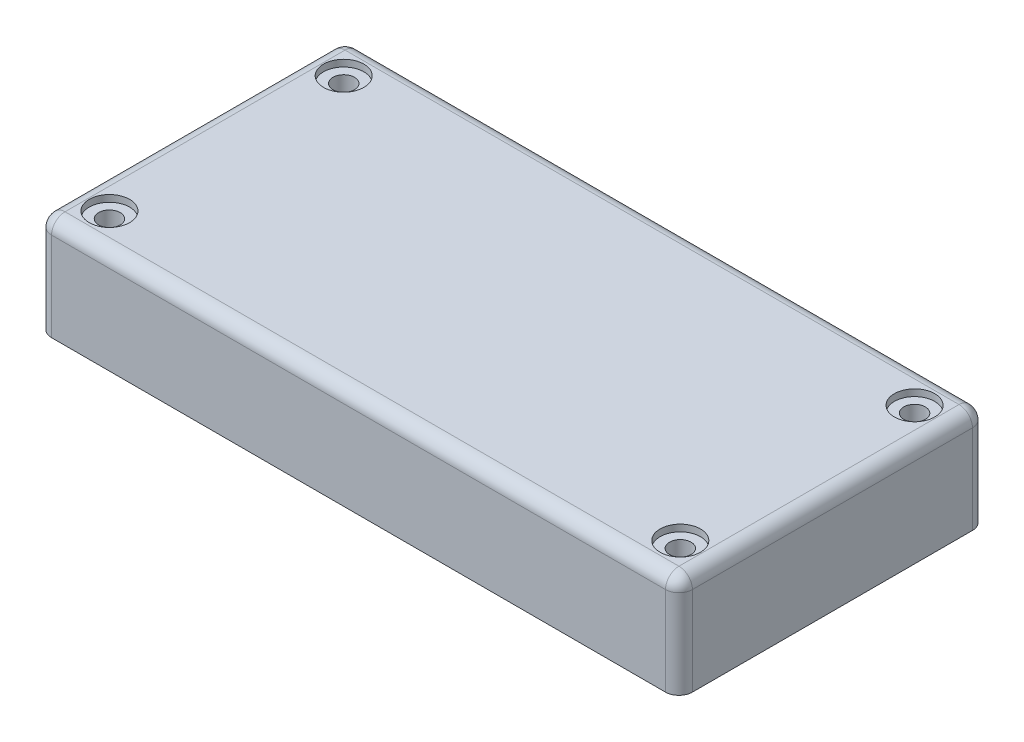
SolidWorks part; units mm, degrees
ref_plane "Спереди" through (0, 0, 0) normal (0, 0, 1) x (1, 0, 0)
ref_plane "Сверху" through (0, 0, 0) normal (0, 1, 0) x (1, 0, 0)
ref_plane "Справа" through (0, 0, 0) normal (1, 0, 0) x (0, 0, -1)
sketch "Эскиз2" plane through (0, 1.2711, 0) normal (0, 1, 0) x (1, 0, 0)
  line L0 (45.2, 0) -> (0, 0) construction
  line L1 (0, 0) -> (45.2, 0)
  line L2 (0, 0) -> (0, 20.4)
  line L3 (0, 20.4) -> (45.2, 20.4)
  line L4 (45.2, 0) -> (45.2, 20.4)
  line L5 (-0.2, -0.2) -> (45.4, -0.2)
  line L6 (-0.2, -0.2) -> (-0.2, 20.6)
  line L7 (-0.2, 20.6) -> (45.4, 20.6)
  line L8 (45.4, -0.2) -> (45.4, 20.6)
  line L9 (46.4, -1.2) -> (46.4, 21.6)
  line L10 (-1.2, 21.6) -> (46.4, 21.6)
  line L11 (-1.2, -1.2) -> (-1.2, 21.6)
  line L12 (-1.2, -1.2) -> (46.4, -1.2)
  dimension "D1" = 0.2
  dimension "D2" = 0.2
  dimension "D3" = 0.2
  dimension "D4" = 0.2
  dimension "D5" = 1
extrude "Бобышка-Вытянуть1" add sketch "Эскиз2" against normal blind 1.6 contours L9 L10 L11 L12 | L6 L5 L8 L7
sketch "Эскиз3" plane through (0, 1.2711, 0) normal (0, 1, 0) x (1, 0, 0)
  line L1 (-1.2, -1.2) -> (46.4, -1.2)
  line L2 (-1.2, -1.2) -> (-1.2, 21.6)
  line L3 (-1.2, 21.6) -> (46.4, 21.6)
  line L4 (46.4, -1.2) -> (46.4, 21.6)
  line L5 (45.4, 20.6) -> (-0.2, 20.6)
  line L6 (45.4, 20.6) -> (45.4, -0.2)
  line L7 (45.4, -0.2) -> (-0.2, -0.2)
  line L8 (-0.2, 20.6) -> (-0.2, -0.2)
extrude "Бобышка-Вытянуть2" add sketch "Эскиз3" along normal blind 2
sketch "Эскиз4" plane through (0, 3.2711, 0) normal (0, 1, 0) x (1, 0, 0)
  line L1 (46.4, -1.2) -> (-1.2, -1.2)
  line L2 (46.4, -1.2) -> (46.4, 21.6)
  line L3 (46.4, 21.6) -> (-1.2, 21.6)
  line L4 (-1.2, -1.2) -> (-1.2, 21.6)
extrude "Бобышка-Вытянуть3" add sketch "Эскиз4" along normal blind 1
sketch "Эскиз5" plane through (0, -0.3289, 0) normal (0, -1, 0) x (1, 0, 0)
  line L1 (-1.2, -21.6) -> (46.4, -21.6)
  line L2 (-1.2, -21.6) -> (-1.2, 1.2)
  line L3 (-1.2, 1.2) -> (46.4, 1.2)
  line L4 (46.4, -21.6) -> (46.4, 1.2)
  line L6 (-0.2, 0.2) -> (45.4, 0.2)
  line L7 (-0.2, 0.2) -> (-0.2, -20.6)
  line L8 (-0.2, -20.6) -> (45.4, -20.6)
  line L9 (45.4, 0.2) -> (45.4, -20.6)
extrude "Бобышка-Вытянуть4" add sketch "Эскиз5" along normal blind 3
sketch "Эскиз6" plane through (0, 0, -21.6) normal (0, 0, -1) x (-1, 0, 0)
  line L0 (1.2, -3.3289) -> (-46.4, -3.3289) construction
  line L1 (-25.5999, -3.3289) -> (-16.9999, -3.3289)
  line L2 (-25.5999, -3.3289) -> (-25.5999, -0.7)
  line L3 (-25.5999, -0.7) -> (-16.9999, -0.7)
  line L4 (-16.9999, -3.3289) -> (-16.9999, -0.7)
  line L5 (-25.2999, -2.5) -> (-25.2999, -1) construction
  line L6 (-17.2999, -1) -> (-17.2999, -2.5) construction
  line L7 (-15.1001, -0.2) -> (-2.7001, -0.2) construction
  line L8 (-15.4001, -3.3289) -> (-2.4001, -3.3289)
  line L9 (-15.4001, -3.3289) -> (-15.4001, 0.1)
  line L10 (-15.4001, 0.1) -> (-2.4001, 0.1)
  line L11 (-2.4001, -3.3289) -> (-2.4001, 0.1)
  line L12 (-42.1499, -0.2) -> (-32.2499, -0.2) construction
  line L13 (-42.4499, -3.3289) -> (-31.9499, -3.3289)
  line L14 (-42.4499, -3.3289) -> (-42.4499, 0.1)
  line L15 (-42.4499, 0.1) -> (-31.9499, 0.1)
  line L16 (-31.9499, -3.3289) -> (-31.9499, 0.1)
  dimension "D1" = 0.3
  dimension "D2" = 0.3
  dimension "D3" = 0.3
  dimension "D4" = 0.3
  dimension "D5" = 0.3
  dimension "D6" = 0.3
  dimension "D7" = 0.3
  dimension "D8" = 0.3
  dimension "D9" = 0.3
extrude "Вырез-Вытянуть1" cut sketch "Эскиз6" against normal up to surface (1 mm away) up to face at (22.6, -0.0289, -20.6)
sketch "Эскиз7" plane through (0, -3.3289, 0) normal (0, -1, 0) x (1, 0, 0)
  line L0 (-1.2, -21.6) -> (-0.2, -20.6) construction
  line L1 (-0.2, 0.2) -> (45.4, 0.2)
  line L2 (-0.2, 0.2) -> (-0.2, -20.6)
  line L3 (-0.2, -20.6) -> (2.4001, -20.6)
  line L4 (45.4, 0.2) -> (45.4, -20.6)
  line L5 (45.4, 0.2) -> (46.4, 1.2) construction
  line L6 (2.4001, -21.1) -> (2.4001, -20.6)
  line L7 (45.9, 0.7) -> (-0.7, 0.7)
  line L8 (45.9, 0.7) -> (45.9, -21.1)
  line L9 (45.9, -21.1) -> (42.4499, -21.1)
  line L10 (-0.7, 0.7) -> (-0.7, -21.1)
  line L11 (2.4001, -20.6) -> (2.4001, -21.6) construction
  line L12 (15.4001, -21.1) -> (15.4001, -20.6)
  line L13 (15.4001, -20.6) -> (15.4001, -21.6) construction
  line L14 (16.9999, -21.1) -> (16.9999, -20.6)
  line L15 (16.9999, -20.6) -> (16.9999, -21.6) construction
  line L16 (25.5999, -21.1) -> (25.5999, -20.6)
  line L17 (25.5999, -20.6) -> (25.5999, -21.6) construction
  line L18 (31.9499, -21.1) -> (31.9499, -20.6)
  line L19 (31.9499, -20.6) -> (31.9499, -21.6) construction
  line L20 (42.4499, -21.1) -> (42.4499, -20.6)
  line L21 (42.4499, -20.6) -> (42.4499, -21.6) construction
  line L22 (2.4001, -21.1) -> (-0.7, -21.1)
  line L23 (15.4001, -20.6) -> (16.9999, -20.6)
  line L24 (16.9999, -21.1) -> (15.4001, -21.1)
  line L25 (25.5999, -20.6) -> (31.9499, -20.6)
  line L26 (31.9499, -21.1) -> (25.5999, -21.1)
  line L27 (42.4499, -20.6) -> (45.4, -20.6)
extrude "Вырез-Вытянуть2" cut sketch "Эскиз7" against normal blind 1
fillet "Скругление1" radius 1 8 edges at (22.6, 4.2711, 1.2) (-1.2, 4.2711, -10.2) (22.6, 4.2711, -21.6) (46.4, 4.2711, -10.2) (46.4, 0.4711, -21.6) (46.4, 0.4711, 1.2) (-1.2, 0.4711, 1.2) (-1.2, 0.4711, -21.6)
sketch "Эскиз8" plane through (0, 3.2711, 0) normal (0, -1, 0) x (1, 0, 0)
  circle A0 centre (1.4, -1.5) radius 0.8
  circle A1 centre (43.8, -1.5) radius 0.8
  circle A2 centre (1.4, -18.9) radius 0.8
  circle A3 centre (43.8, -18.9) radius 0.8
  dimension "D1" = 1.6
extrude "Вырез-Вытянуть3" cut sketch "Эскиз8" against normal up to surface (1 mm away) up to face at (22.6, 4.2711, -10.2)
sketch "Эскиз10" plane through (0, 4.2711, 0) normal (0, 1, 0) x (1, 0, 0)
  circle A0 centre (1.4, 18.9) radius 1.5
  circle A1 centre (1.4, 1.5) radius 1.5
  circle A2 centre (43.8, 1.5) radius 1.5
  circle A3 centre (43.8, 18.9) radius 1.5
  dimension "D1" = 3
extrude "Вырез-Вытянуть4" cut sketch "Эскиз10" against normal blind 0.5
sketch "Эскиз11" plane through (0, 3.2711, 0) normal (0, -1, 0) x (1, 0, 0)
  line L1 (45.4, 0.2) -> (42.3, 0.2)
  line L2 (45.4, 0.2) -> (45.4, -3)
  line L3 (45.4, -3) -> (42.3, -3)
  line L4 (42.3, 0.2) -> (42.3, -3)
  line L5 (45.4, -20.6) -> (42.3, -20.6)
  line L6 (45.4, -20.6) -> (45.4, -17.4)
  line L7 (45.4, -17.4) -> (42.3, -17.4)
  line L8 (42.3, -20.6) -> (42.3, -17.4)
  line L9 (-0.2, 0.2) -> (2.9, 0.2)
  line L10 (-0.2, 0.2) -> (-0.2, -3)
  line L11 (-0.2, -3) -> (2.9, -3)
  line L12 (2.9, 0.2) -> (2.9, -3)
  line L13 (-0.2, -20.6) -> (2.9, -20.6)
  line L14 (-0.2, -20.6) -> (-0.2, -17.4)
  line L15 (-0.2, -17.4) -> (2.9, -17.4)
  line L16 (2.9, -20.6) -> (2.9, -17.4)
  circle A0 centre (1.4, -1.5) radius 0.8 construction
  dimension "D2" = 1.5
  dimension "D1" = 1.5
extrude "Бобышка-Вытянуть5" add sketch "Эскиз11" along normal blind 1
sketch "Эскиз12" plane through (0, 2.2711, 0) normal (0, -1, 0) x (1, 0, 0)
  circle A0 centre (1.4, -1.5) radius 0.8
  circle A1 centre (1.4, -1.5) radius 0.8 construction
  circle A2 centre (1.4, -18.9) radius 0.8
  circle A3 centre (1.4, -18.9) radius 0.8 construction
  circle A4 centre (43.8, -18.9) radius 0.8
  circle A5 centre (43.8, -1.5) radius 0.8
extrude "Вырез-Вытянуть6" cut sketch "Эскиз12" against normal up to surface (1.5 mm away) up to face at (43.8, 3.7711, -17.4)
